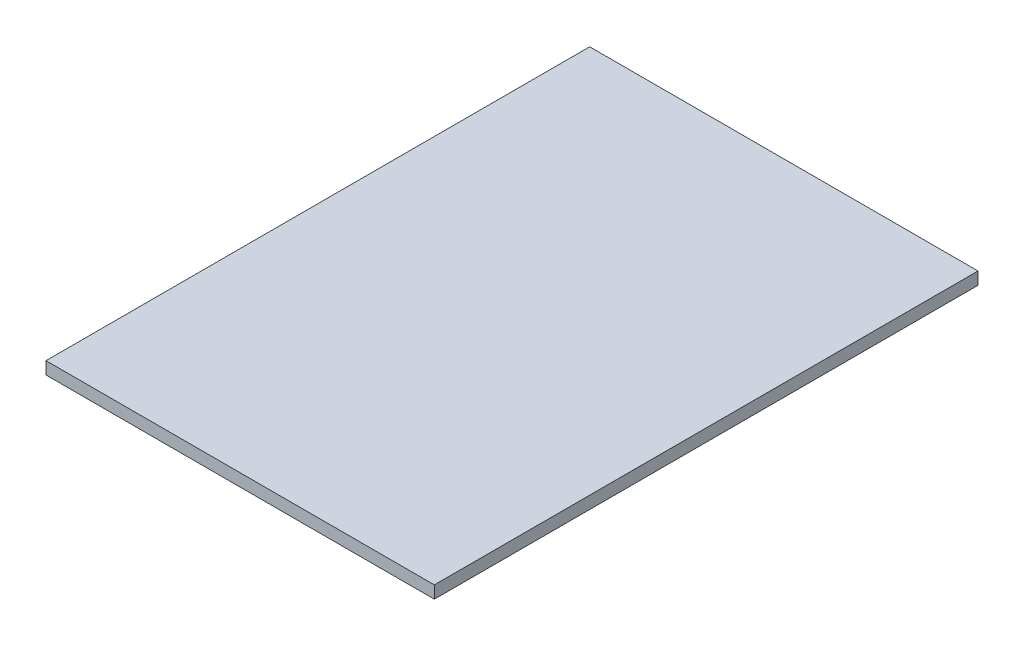
SolidWorks part; units mm, degrees
ref_plane "Płaszczyzna przednia" through (0, 0, 0) normal (0, 0, 1) x (1, 0, 0)
ref_plane "Płaszczyzna górna" through (0, 0, 0) normal (0, 1, 0) x (1, 0, 0)
ref_plane "Płaszczyzna prawa" through (0, 0, 0) normal (1, 0, 0) x (0, 0, -1)
sketch "Sketch1" plane through (0, 0, 0) normal (0, 1, 0) x (1, 0, 0)
  line L1 (-30, -49.8246) -> (20, -49.8246)
  line L2 (-30, -49.8246) -> (-30, 20.1754)
  line L3 (-30, 20.1754) -> (20, 20.1754)
  line L4 (20, -49.8246) -> (20, 20.1754)
  dimension "D1" = 50
  dimension "D2" = 70
extrude "Boss-Extrude1" add sketch "Sketch1" along normal blind 1.6
